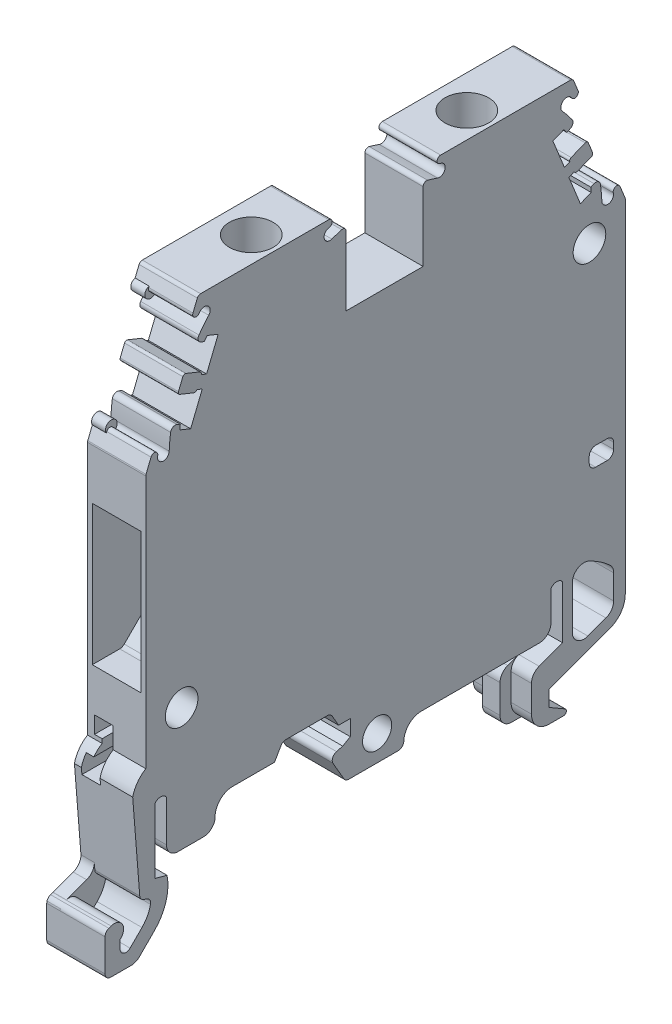
SolidWorks part; units mm, degrees
ref_plane "Front Plane" through (0, 0, 0) normal (0, 0, 1) x (1, 0, 0)
ref_plane "Top Plane" through (0, 0, 0) normal (0, 1, 0) x (1, 0, 0)
ref_plane "Right Plane" through (0, 0, 0) normal (1, 0, 0) x (0, 0, -1)
ref_plane "Plane1" through (0, 0, 0) normal (1, 0, 0) x (0, 0, -1)
sketch "Sketch1" plane through (0, 0, 0) normal (1, 0, 0) x (0, 0, -1)
  line L0 (-23.502, -46.95) -> (-21.759, -46.95)
  line L1 (-21.0519, -46.6571) -> (-19.7733, -45.3782)
  line L2 (-18.6758, -41.785) -> (-19.727, -41.5031)
  line L3 (-19.727, -41.5031) -> (-19.727, -35.95)
  line L4 (-18.727, -35.95) -> (-18.727, -39.5)
  line L5 (-17.727, -40.5) -> (-15.552, -40.5)
  line L6 (-13.052, -38) -> (-9.452, -38)
  line L7 (-9.452, -38) -> (-8.9029, -37.0498)
  line L8 (-8.47, -36.8) -> (-4.933, -36.8)
  line L9 (-4.4999, -37.0502) -> (-3.952, -38)
  line L10 (-3.952, -38) -> (-2.952, -38)
  line L11 (-2.952, -38) -> (-2.952, -39.35)
  line L12 (-2.952, -39.35) -> (-3.601, -39.725)
  line L13 (-3.601, -39.725) -> (-4.1314, -39.8671)
  line L14 (-4.4613, -40.5468) -> (-3.4657, -42.2532)
  line L15 (-3.068, -42.45) -> (1.149, -42.45)
  line L16 (3.148, -40.5) -> (13.273, -40.5)
  line L17 (14.273, -39.5) -> (14.273, -36.95)
  line L18 (15.273, -36.95) -> (15.273, -41.4863)
  line L19 (15.273, -41.4863) -> (13.256, -42.2202)
  line L20 (12.598, -43.16) -> (12.598, -45.45)
  line L21 (14.098, -46.95) -> (15.355, -46.9502)
  line L22 (15.4769, -46.4961) -> (14.098, -45.7)
  line L23 (14.098, -45.7) -> (14.098, -44.35)
  line L24 (14.098, -44.35) -> (19.332, -42.4452)
  line L25 (20.648, -40.566) -> (20.648, -33.868)
  line L26 (20.648, -33.868) -> (20.648, -11.196)
  line L27 (20.6261, -11.0838) -> (20.1976, -10.0227)
  line L28 (17.9711, -8.7076) -> (17.687, -8.822)
  line L29 (17.687, -8.822) -> (17.724, -9.239)
  line L30 (17.724, -9.239) -> (16.797, -9.613)
  line L31 (16.797, -9.613) -> (15.804, -7.156)
  line L32 (15.804, -7.156) -> (16.2677, -6.9691)
  line L33 (16.528, -7.0797) -> (17.733, -6.5927)
  line L34 (17.8437, -6.332) -> (17.4692, -5.405)
  line L35 (17.209, -5.2948) -> (16.0035, -5.7818)
  line L36 (15.8927, -6.0421) -> (15.429, -6.229)
  line L37 (15.429, -6.229) -> (14.437, -3.772)
  line L38 (14.437, -3.772) -> (15.364, -3.398)
  line L39 (15.364, -3.398) -> (15.627, -3.723)
  line L40 (15.627, -3.723) -> (15.9109, -3.6079)
  line L41 (16.5991, -1.1153) -> (16.2241, -0.1878)
  line L42 (15.946, 0) -> (4.802, 0.0002)
  line L43 (3.298, -1.592) -> (3.298, -7.525)
  line L44 (3.298, -7.525) -> (-3.302, -7.525)
  line L45 (-3.302, -7.525) -> (-3.302, -1.592)
  line L46 (-4.805, 0.0002) -> (-15.799, 0)
  line L47 (-16.0776, -0.1878) -> (-16.4522, -1.1155)
  line L48 (-15.7639, -3.6079) -> (-15.481, -3.723)
  line L49 (-15.481, -3.723) -> (-15.217, -3.398)
  line L50 (-15.217, -3.398) -> (-14.29, -3.772)
  line L51 (-14.29, -3.772) -> (-15.283, -6.229)
  line L52 (-15.283, -6.229) -> (-15.7465, -6.0418)
  line L53 (-15.857, -5.7818) -> (-17.062, -5.2948)
  line L54 (-17.3227, -5.405) -> (-17.6972, -6.332)
  line L55 (-17.587, -6.5927) -> (-16.3815, -7.0797)
  line L56 (-16.1215, -6.9688) -> (-15.657, -7.156)
  line L57 (-15.657, -7.156) -> (-16.65, -9.613)
  line L58 (-16.65, -9.613) -> (-17.577, -9.239)
  line L59 (-17.577, -9.239) -> (-17.541, -8.822)
  line L60 (-17.541, -8.822) -> (-17.8241, -8.7076)
  line L61 (-20.0511, -10.0227) -> (-20.4801, -11.0838)
  line L62 (-20.502, -11.196) -> (-20.502, -32.9505)
  line L63 (-21.6267, -34.5031) -> (-21.0202, -42.1577)
  line L64 (-20.6519, -42.6008) -> (-20.4543, -42.654)
  line L65 (-20.8274, -44.5941) -> (-21.8482, -45.6148)
  line L66 (-22.702, -45.261) -> (-22.702, -44.5345)
  line L67 (-23.4754, -43.1581) -> (-23.673, -43.2301)
  line L68 (-24.002, -43.7) -> (-24.002, -46.45)
  arc A0 (-24.002, -46.45) -> (-23.502, -46.95) centre (-23.502, -46.45) ccw
  arc A1 (-21.759, -46.95) -> (-21.0519, -46.6571) centre (-21.7589, -45.9505) ccw
  arc A2 (-19.7733, -45.3782) -> (-18.6758, -41.785) centre (-22.6022, -42.55) ccw
  arc A3 (-19.727, -35.95) -> (-18.727, -35.95) centre (-19.227, -36.2817) cw
  arc A4 (-18.727, -39.5) -> (-17.727, -40.5) centre (-17.727, -39.5) ccw
  arc A5 (-15.552, -40.5) -> (-14.552, -39.5) centre (-15.552, -39.5) ccw
  arc A6 (-14.552, -39.5) -> (-13.052, -38) centre (-13.052, -39.5) cw
  arc A7 (-8.9029, -37.0498) -> (-8.47, -36.8) centre (-8.47, -37.3) cw
  arc A8 (-4.933, -36.8) -> (-4.4999, -37.0502) centre (-4.933, -37.3) cw
  arc A9 (-4.1314, -39.8671) -> (-4.4613, -40.5468) centre (-4.0024, -40.3497) ccw
  arc A10 (-3.4657, -42.2532) -> (-3.068, -42.45) centre (-3.0679, -41.9495) ccw
  arc A11 (1.149, -42.45) -> (1.6487, -41.9625) centre (1.1491, -41.9503) ccw
  arc A12 (1.6487, -41.9625) -> (3.148, -40.5) centre (3.1479, -41.9997) cw
  arc A13 (13.273, -40.5) -> (14.273, -39.5) centre (13.273, -39.5) ccw
  arc A14 (14.273, -36.95) -> (15.273, -36.95) centre (14.773, -37.2817) cw
  arc A15 (13.256, -42.2202) -> (12.598, -43.16) centre (13.5984, -43.1601) ccw
  arc A16 (12.598, -45.45) -> (14.098, -46.95) centre (14.098, -45.45) ccw
  arc A17 (15.355, -46.9502) -> (15.4769, -46.4961) centre (15.3551, -46.7068) ccw
  arc A18 (19.332, -42.4452) -> (20.648, -40.566) centre (18.6485, -40.5662) ccw
  arc A19 (20.648, -11.196) -> (20.6261, -11.0838) centre (20.3519, -11.1956) ccw
  arc A20 (20.1976, -10.0227) -> (19.6227, -10.2127) centre (19.9162, -10.136) ccw
  arc A21 (19.6227, -10.2127) -> (18.6394, -10.3596) centre (19.1389, -10.339) cw
  arc A22 (18.6394, -10.3596) -> (18.5169, -9.0219) centre (5.0719, -10.9273) ccw
  arc A23 (18.5169, -9.0219) -> (17.9711, -8.7076) centre (18.1215, -9.0775) ccw
  arc A24 (16.2677, -6.9691) -> (16.528, -7.0797) centre (16.4534, -6.8936) ccw
  arc A25 (17.733, -6.5927) -> (17.8437, -6.332) centre (17.6571, -6.4066) ccw
  arc A26 (17.4692, -5.405) -> (17.209, -5.2948) centre (17.2842, -5.4794) ccw
  arc A27 (16.0035, -5.7818) -> (15.8927, -6.0421) centre (16.0773, -5.967) ccw
  arc A28 (15.9109, -3.6079) -> (16.0848, -3.0023) centre (15.761, -3.2371) ccw
  arc A29 (16.0848, -3.0023) -> (15.244, -1.9551) centre (5.0525, -10.999) ccw
  arc A30 (15.244, -1.9551) -> (16.0537, -1.3777) centre (15.6179, -1.6231) cw
  arc A31 (16.0537, -1.3777) -> (16.5991, -1.1153) centre (16.318, -1.2291) ccw
  arc A32 (16.2241, -0.1878) -> (15.946, 0) centre (15.9461, -0.2996) ccw
  arc A33 (4.802, 0.0002) -> (4.7626, -0.604) centre (4.802, -0.3032) ccw
  arc A34 (4.7626, -0.604) -> (4.5326, -1.5717) centre (4.698, -1.0998) cw
  arc A35 (4.5326, -1.5717) -> (3.6786, -1.3031) centre (0.0081, -14.4641) ccw
  arc A36 (3.6786, -1.3031) -> (3.298, -1.592) centre (3.5979, -1.592) ccw
  arc A37 (-3.302, -1.592) -> (-3.6826, -1.3031) centre (-3.6019, -1.592) ccw
  arc A38 (-3.6826, -1.3031) -> (-4.5366, -1.5717) centre (-0.0121, -14.4641) ccw
  arc A39 (-4.5366, -1.5717) -> (-4.7661, -0.604) centre (-4.702, -1.0999) cw
  arc A40 (-4.7661, -0.604) -> (-4.805, 0.0002) centre (-4.805, -0.3032) ccw
  arc A41 (-15.799, 0) -> (-16.0776, -0.1878) centre (-15.7987, -0.3009) ccw
  arc A42 (-16.4522, -1.1155) -> (-15.9067, -1.3777) centre (-16.171, -1.2291) ccw
  arc A43 (-15.9067, -1.3777) -> (-15.0975, -1.9551) centre (-15.471, -1.6229) cw
  arc A44 (-15.0975, -1.9551) -> (-15.9383, -3.0023) centre (-5.1505, -10.8028) ccw
  arc A45 (-15.9383, -3.0023) -> (-15.7639, -3.6079) centre (-15.6136, -3.2367) ccw
  arc A46 (-15.7465, -6.0418) -> (-15.857, -5.7818) centre (-15.9317, -5.967) ccw
  arc A47 (-17.062, -5.2948) -> (-17.3227, -5.405) centre (-17.1372, -5.4803) ccw
  arc A48 (-17.6972, -6.332) -> (-17.587, -6.5927) centre (-17.5117, -6.4072) ccw
  arc A49 (-16.3815, -7.0797) -> (-16.1215, -6.9688) centre (-16.3071, -6.8939) ccw
  arc A50 (-17.8241, -8.7076) -> (-18.3704, -9.0219) centre (-17.9744, -9.0782) ccw
  arc A51 (-18.3704, -9.0219) -> (-18.4929, -10.3596) centre (-5.3188, -10.8913) ccw
  arc A52 (-18.4929, -10.3596) -> (-19.4762, -10.2127) centre (-18.9924, -10.339) cw
  arc A53 (-19.4762, -10.2127) -> (-20.0511, -10.0227) centre (-19.7697, -10.1362) ccw
  arc A54 (-20.4801, -11.0838) -> (-20.502, -11.196) centre (-20.2059, -11.1956) ccw
  arc A55 (-20.502, -32.9505) -> (-21.6267, -34.5031) centre (-19.1924, -35.0827) ccw
  arc A56 (-21.0202, -42.1577) -> (-20.6519, -42.6008) centre (-20.5225, -42.1186) ccw
  arc A57 (-20.4543, -42.654) -> (-20.0946, -43.2398) centre (-20.5842, -43.1371) cw
  arc A58 (-20.0946, -43.2398) -> (-20.8274, -44.5941) centre (-22.7392, -42.6843) cw
  arc A59 (-21.8482, -45.6148) -> (-22.702, -45.261) centre (-22.2017, -45.2608) cw
  arc A60 (-22.702, -44.5345) -> (-23.4754, -43.1581) centre (-23.202, -43.91) ccw
  arc A61 (-23.673, -43.2301) -> (-24.002, -43.7) centre (-23.5018, -43.7001) ccw
extrude "Extrude1" add sketch "Sketch1" along normal blind 5
ref_plane "Plane2" through (5, 0, 0) normal (1, 0, 0) x (0, 0, -1)
sketch "Sketch2" plane through (5, 0, 0) normal (1, 0, 0) x (0, 0, -1)
  line L0 (16.1, -37.442) -> (16.1, -41.126)
  line L1 (17.442, -42.0658) -> (18.992, -41.5018)
  line L2 (19.65, -40.562) -> (19.65, -38.47)
  arc A0 (16.1, -41.126) -> (17.442, -42.0658) centre (17.1002, -41.1259) ccw
  arc A1 (18.992, -41.5018) -> (19.65, -40.562) centre (18.6496, -40.5619) ccw
  arc A2 (19.65, -38.47) -> (19.325, -37.7322) centre (18.6502, -38.47) ccw
  arc A3 (19.325, -37.7322) -> (17.5166, -36.5333) centre (14.5918, -42.9078) ccw
  arc A4 (17.5166, -36.5333) -> (16.1, -37.442) centre (17.0997, -37.4418) ccw
extrude "Extrude2" cut sketch "Sketch2" against normal blind 5
ref_plane "Plane3" through (5, 0, 0) normal (1, 0, 0) x (0, 0, -1)
sketch "Sketch3" plane through (5, 0, 0) normal (1, 0, 0) x (0, 0, -1)
  circle A0 centre (-17.425, -29.947) radius 1.4
extrude "Extrude3" cut sketch "Sketch3" against normal blind 2.3
ref_plane "Plane4" through (5, 0, 0) normal (1, 0, 0) x (0, 0, -1)
sketch "Sketch4" plane through (5, 0, 0) normal (1, 0, 0) x (0, 0, -1)
  circle A0 centre (17.575, -12.947) radius 1.4
extrude "Extrude4" cut sketch "Sketch4" against normal blind 3.5
ref_plane "Plane5" through (0, 0, 0) normal (1, 0, 0) x (0, 0, -1)
sketch "Sketch5" plane through (0, 0, 0) normal (1, 0, 0) x (0, 0, -1)
  line L0 (-23.502, -46.95) -> (-21.759, -46.95)
  line L1 (-21.0519, -46.6571) -> (-19.7733, -45.3782)
  line L2 (-18.6758, -41.785) -> (-19.552, -41.55)
  line L3 (-19.552, -41.55) -> (-21.0701, -41.503)
  line L4 (-21.725, -42.5218) -> (-23.6729, -43.2301)
  line L5 (-24.002, -43.7) -> (-24.002, -46.45)
  arc A0 (-24.002, -46.45) -> (-23.502, -46.95) centre (-23.502, -46.45) ccw
  arc A1 (-21.759, -46.95) -> (-21.0519, -46.6571) centre (-21.7589, -45.9505) ccw
  arc A2 (-19.7733, -45.3782) -> (-18.6758, -41.785) centre (-22.6022, -42.55) ccw
  arc A3 (-21.0701, -41.503) -> (-21.725, -42.5218) centre (-22.0674, -41.5819) cw
  arc A4 (-23.6729, -43.2301) -> (-24.002, -43.7) centre (-23.502, -43.7) ccw
extrude "Extrude5" add sketch "Sketch5" along normal blind 1.15
ref_plane "Plane6" through (5, 0, 0) normal (1, 0, 0) x (0, 0, -1)
sketch "Sketch6" plane through (5, 0, 0) normal (1, 0, 0) x (0, 0, -1)
  circle A0 centre (-0.65, -40.25) radius 1.25
extrude "Extrude6" cut sketch "Sketch6" against normal blind 5 and the other way blind 5
ref_plane "Plane7" through (5, 0, 0) normal (1, 0, 0) x (0, 0, -1)
sketch "Sketch7" plane through (5, 0, 0) normal (1, 0, 0) x (0, 0, -1)
  line L0 (18.106, -29.847) -> (19.1, -29.847)
  line L1 (19.65, -29.297) -> (19.65, -28.772)
  line L2 (19.1, -28.222) -> (18.106, -28.222)
  line L3 (17.556, -28.772) -> (17.556, -29.297)
  arc A0 (17.556, -29.297) -> (18.106, -29.847) centre (18.106, -29.297) ccw
  arc A1 (19.1, -29.847) -> (19.65, -29.297) centre (19.1, -29.297) ccw
  arc A2 (19.65, -28.772) -> (19.1, -28.222) centre (19.1, -28.772) ccw
  arc A3 (18.106, -28.222) -> (17.556, -28.772) centre (18.106, -28.772) ccw
extrude "Extrude7" cut sketch "Sketch7" against normal blind 4
ref_plane "Plane8" through (1.75, 0, 0) normal (1, 0, 0) x (0, 0, -1)
sketch "Sketch8" plane through (1.75, 0, 0) normal (1, 0, 0) x (0, 0, -1)
  line L0 (12.648, -46.95) -> (14.2, -46.95)
  line L1 (14.2, -46.95) -> (14.2, -41.9496)
  line L2 (14.2, -41.9496) -> (14, -41.9496)
  line L3 (14, -41.9496) -> (12.306, -42.5662)
  line L4 (11.648, -43.506) -> (11.648, -45.95)
  arc A0 (11.648, -45.95) -> (12.648, -46.95) centre (12.648, -45.95) ccw
  arc A1 (12.306, -42.5662) -> (11.648, -43.506) centre (12.6484, -43.5061) ccw
extrude "Extrude8" add sketch "Sketch8" along normal blind 1.5
ref_plane "Plane9" through (2.8, 0, 0) normal (1, 0, 0) x (0, 0, -1)
sketch "Sketch9" plane through (2.8, 0, 0) normal (1, 0, 0) x (0, 0, -1)
  line L0 (9.25, 1) -> (11.125, 1)
  line L1 (11.125, 1) -> (11.125, -11.05)
  line L2 (11.125, -11.05) -> (10.665, -11.05)
  line L3 (10.665, -11.05) -> (10.665, -14)
  line L4 (10.665, -14) -> (9.25, -14)
  line L5 (9.25, -14) -> (9.25, 1)
  line L6 (9.25, -14) -> (9.25, 1) construction
revolve "Cut-Revolve1" cut sketch "Sketch9" angle 360 about L6 reverse direction yes
ref_plane "Plane10" through (2.8, 0, 0) normal (1, 0, 0) x (0, 0, -1)
sketch "Sketch10" plane through (2.8, 0, 0) normal (1, 0, 0) x (0, 0, -1)
  line L0 (-9.25, 1) -> (-7.375, 1)
  line L1 (-7.375, 1) -> (-7.375, -11.05)
  line L2 (-7.375, -11.05) -> (-7.835, -11.05)
  line L3 (-7.835, -11.05) -> (-7.835, -14)
  line L4 (-7.835, -14) -> (-9.25, -14)
  line L5 (-9.25, -14) -> (-9.25, 1)
  line L6 (-9.25, -14) -> (-9.25, 1) construction
revolve "Cut-Revolve2" cut sketch "Sketch10" angle 360 about L6 reverse direction yes
ref_plane "Plane11" through (0, 0, 0) normal (1, 0, 0) x (0, 0, -1)
sketch "Sketch11" plane through (0, 0, 0) normal (1, 0, 0) x (0, 0, -1)
  circle A0 centre (-16.29, -1.51) radius 0.5
extrude "Extrude9" add sketch "Sketch11" along normal blind 1.2
ref_plane "Plane12" through (0, 0, 0) normal (1, 0, 0) x (0, 0, -1)
sketch "Sketch12" plane through (0, 0, 0) normal (1, 0, 0) x (0, 0, -1)
  circle A0 centre (16.44, -1.51) radius 0.5
extrude "Extrude10" add sketch "Sketch12" along normal blind 1.2
ref_plane "Plane13" through (0, 0, 0) normal (1, 0, 0) x (0, 0, -1)
sketch "Sketch13" plane through (0, 0, 0) normal (1, 0, 0) x (0, 0, -1)
  circle A0 centre (19.81, -9.85) radius 0.5
extrude "Extrude11" add sketch "Sketch13" along normal blind 1.2
ref_plane "Plane14" through (0, 0, 0) normal (1, 0, 0) x (0, 0, -1)
sketch "Sketch14" plane through (0, 0, 0) normal (1, 0, 0) x (0, 0, -1)
  circle A0 centre (-19.66, -9.85) radius 0.5
extrude "Extrude12" add sketch "Sketch14" along normal blind 1.2
ref_plane "Plane15" through (0.41, 0, 0) normal (1, 0, 0) x (0, 0, -1)
sketch "Sketch15" plane through (0.41, 0, 0) normal (1, 0, 0) x (0, 0, -1)
  line L0 (14.48, -18.96) -> (14.48, -24.08)
  line L1 (14.48, -24.08) -> (17.7589, -27.3589)
  line L2 (18.1478, -27.52) -> (20.65, -27.52)
  line L3 (20.65, -27.52) -> (20.65, -15.52)
  line L4 (20.65, -15.52) -> (18.1478, -15.52)
  line L5 (17.7589, -15.6811) -> (14.48, -18.96)
  arc A0 (17.7589, -27.3589) -> (18.1478, -27.52) centre (18.1478, -26.97) ccw
  arc A1 (18.1478, -15.52) -> (17.7589, -15.6811) centre (18.1478, -16.07) ccw
extrude "Extrude13" cut sketch "Sketch15" along normal blind 4.17
ref_plane "Plane16" through (0.41, 0, 0) normal (1, 0, 0) x (0, 0, -1)
sketch "Sketch16" plane through (0.41, 0, 0) normal (1, 0, 0) x (0, 0, -1)
  line L0 (-20.65, -15.52) -> (-20.65, -27.52)
  line L1 (-20.65, -27.52) -> (-18.1478, -27.52)
  line L2 (-17.7589, -27.3589) -> (-14.48, -24.08)
  line L3 (-14.48, -24.08) -> (-14.48, -18.96)
  line L4 (-14.48, -18.96) -> (-17.7589, -15.6811)
  line L5 (-18.1478, -15.52) -> (-20.65, -15.52)
  arc A0 (-18.1478, -27.52) -> (-17.7589, -27.3589) centre (-18.1478, -26.97) ccw
  arc A1 (-17.7589, -15.6811) -> (-18.1478, -15.52) centre (-18.1478, -16.07) ccw
extrude "Extrude14" cut sketch "Sketch16" along normal blind 4.17
ref_plane "Plane17" through (0, 0, -22) normal (0, 0, 1) x (1, 0, 0)
sketch "Sketch17" plane through (0, 0, -22) normal (0, 0, 1) x (1, 0, 0)
  line L0 (1.65, -22.57) -> (4.09, -22.57)
  line L1 (4.59, -22.07) -> (4.59, -19.7)
  line L2 (4.09, -19.2) -> (1.65, -19.2)
  line L3 (1.15, -19.7) -> (1.15, -22.07)
  arc A0 (1.15, -22.07) -> (1.65, -22.57) centre (1.65, -22.07) ccw
  arc A1 (4.09, -22.57) -> (4.59, -22.07) centre (4.09, -22.07) ccw
  arc A2 (4.59, -19.7) -> (4.09, -19.2) centre (4.09, -19.7) ccw
  arc A3 (1.65, -19.2) -> (1.15, -19.7) centre (1.65, -19.7) ccw
extrude "Extrude15" cut sketch "Sketch17" along normal blind 16.5
ref_plane "Plane18" through (0, 0, -22) normal (0, 0, 1) x (1, 0, 0)
sketch "Sketch18" plane through (0, 0, -22) normal (0, 0, 1) x (1, 0, 0)
  line L0 (0.6, -31.15) -> (0.6, -32.6)
  line L1 (0.6, -32.6) -> (1.25, -32.6)
  line L2 (1.25, -32.6) -> (1.25, -33.6)
  line L3 (1.25, -33.6) -> (0.6, -33.6)
  line L4 (0.6, -33.6) -> (0.6, -35.05)
  line L5 (0.6, -35.05) -> (2.2, -35.05)
  line L6 (2.2, -35.05) -> (2.2, -31.15)
  line L7 (2.2, -31.15) -> (0.6, -31.15)
extrude "Extrude16" cut sketch "Sketch18" along normal blind 5.442
ref_plane "Plane19" through (0, 0, 22) normal (0, 0, 1) x (1, 0, 0)
sketch "Sketch19" plane through (0, 0, 22) normal (0, 0, 1) x (1, 0, 0)
  line L0 (1.15, -19.7) -> (1.15, -22.07)
  line L1 (1.65, -22.57) -> (4.09, -22.57)
  line L2 (4.59, -22.07) -> (4.59, -19.7)
  line L3 (4.09, -19.2) -> (1.65, -19.2)
  arc A0 (1.15, -22.07) -> (1.65, -22.57) centre (1.65, -22.07) ccw
  arc A1 (4.09, -22.57) -> (4.59, -22.07) centre (4.09, -22.07) ccw
  arc A2 (4.59, -19.7) -> (4.09, -19.2) centre (4.09, -19.7) ccw
  arc A3 (1.65, -19.2) -> (1.15, -19.7) centre (1.65, -19.7) ccw
extrude "Extrude17" cut sketch "Sketch19" against normal blind 16.5
ref_plane "Plane20" through (0, 0, 22) normal (0, 0, 1) x (1, 0, 0)
sketch "Sketch20" plane through (0, 0, 22) normal (0, 0, 1) x (1, 0, 0)
  line L0 (0.6, -31.15) -> (0.6, -32.6)
  line L1 (0.6, -32.6) -> (1.25, -32.6)
  line L2 (1.25, -32.6) -> (1.25, -33.6)
  line L3 (1.25, -33.6) -> (0.6, -33.6)
  line L4 (0.6, -33.6) -> (0.6, -35.05)
  line L5 (0.6, -35.05) -> (2.2, -35.05)
  line L6 (2.2, -35.05) -> (2.2, -31.15)
  line L7 (2.2, -31.15) -> (0.6, -31.15)
extrude "Extrude18" cut sketch "Sketch20" against normal blind 5.588
ref_plane "Plane21" through (-2, 0, 0) normal (1, 0, 0) x (0, 0, -1)
sketch "Sketch21" plane through (-2, 0, 0) normal (1, 0, 0) x (0, 0, -1)
  line L0 (20.63, -36.8088) -> (20.63, -33.7701)
  line L1 (16.63, -32.1596) -> (16.63, -34.5872)
  arc A0 (16.63, -34.5872) -> (20.63, -36.8088) centre (14.63, -42.9) cw
  arc A1 (20.63, -33.7701) -> (16.63, -32.1596) centre (14.63, -42.9) ccw
extrude "Extrude19" add sketch "Sketch21" along normal blind 2
